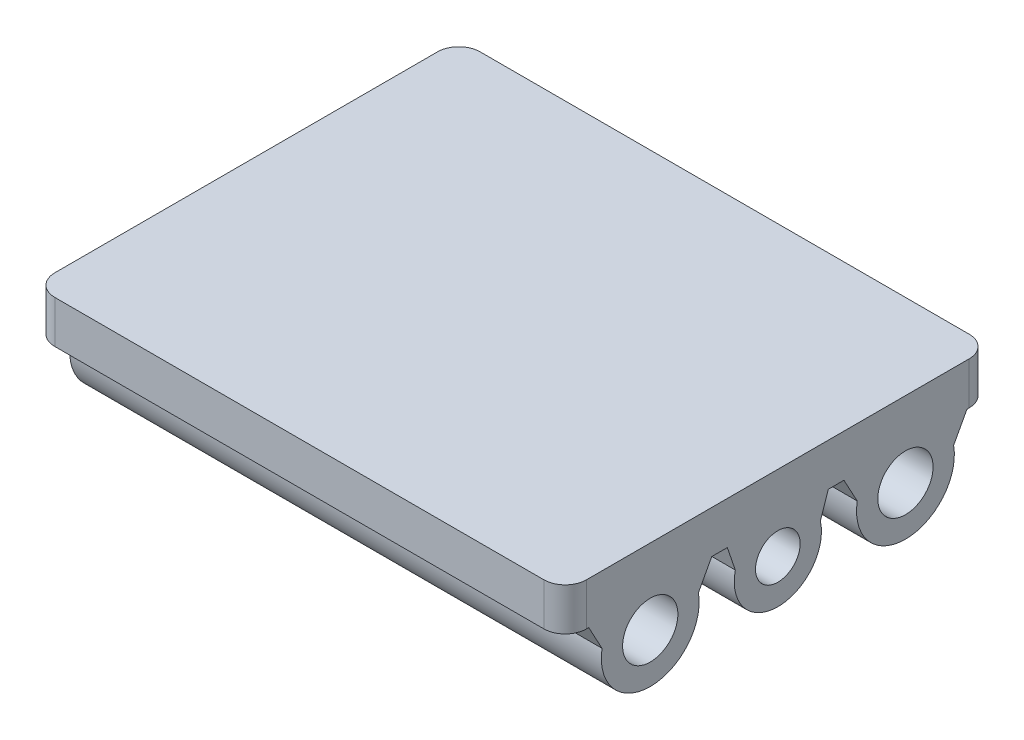
SolidWorks part; units mm, degrees
ref_plane "Front Plane" through (0, 0, 0) normal (0, 0, 1) x (1, 0, 0)
ref_plane "Top Plane" through (0, 0, 0) normal (0, 1, 0) x (1, 0, 0)
ref_plane "Right Plane" through (0, 0, 0) normal (1, 0, 0) x (0, 0, -1)
sketch "Sketch1" plane through (0, 0, 0) normal (0, 1, 0) x (1, 0, 0)
  line L1 (-125, 100) -> (125, 100)
  line L2 (-125, 100) -> (-125, -100)
  line L3 (-125, -100) -> (125, -100)
  line L4 (125, 100) -> (125, -100)
  line L5 (-125, 100) -> (125, -100) construction
  line L6 (-125, -100) -> (125, 100) construction
  point P0 (0, 0)
  dimension "D1" = 250
  dimension "D2" = 200
extrude "Boss-Extrude1" add sketch "Sketch1" along normal blind 20
sketch "Sketch2" plane through (-125, 0, 0) normal (-1, 0, 0) x (0, 0, 1)
  line L1 (0, -15.5) -> (0, 28.4386) construction
  line L3 (-100, 0) -> (100, 0) construction
  circle A0 centre (-60, -15.5) radius 13
  circle A1 centre (0, -15.5) radius 10.5
  circle A2 centre (0, -15.5) radius 20.5
  circle A3 centre (-60, -15.5) radius 23
  circle A4 centre (60, -15.5) radius 13
  circle A5 centre (60, -15.5) radius 23
  dimension "D1" = 26
  dimension "D2" = 21
  dimension "D5" = 5
  dimension "D6" = 60
  dimension "D3" = 10
  dimension "D4" = 10
extrude "Boss-Extrude2" add sketch "Sketch2" against normal up to surface (250 mm away) up to face at (125, 10, 0)
chamfer "Chamfer1" distance 20 angle 60 6 edges at (0, 0, -76.9926) (0, 0, -43.0074) (0, 0, -13.4164) (0, 0, 13.4164) (0, 0, 43.0074) (0, 0, 76.9926) first distance on face at (0, -19.25, -60) first distance on face at (0, -18, 0) first distance on face at (0, -19.25, 60)
fillet "Fillet1" radius 10 4 edges at (125, 10, 100) (125, 10, -100) (-125, 10, -100) (-125, 10, 100)
